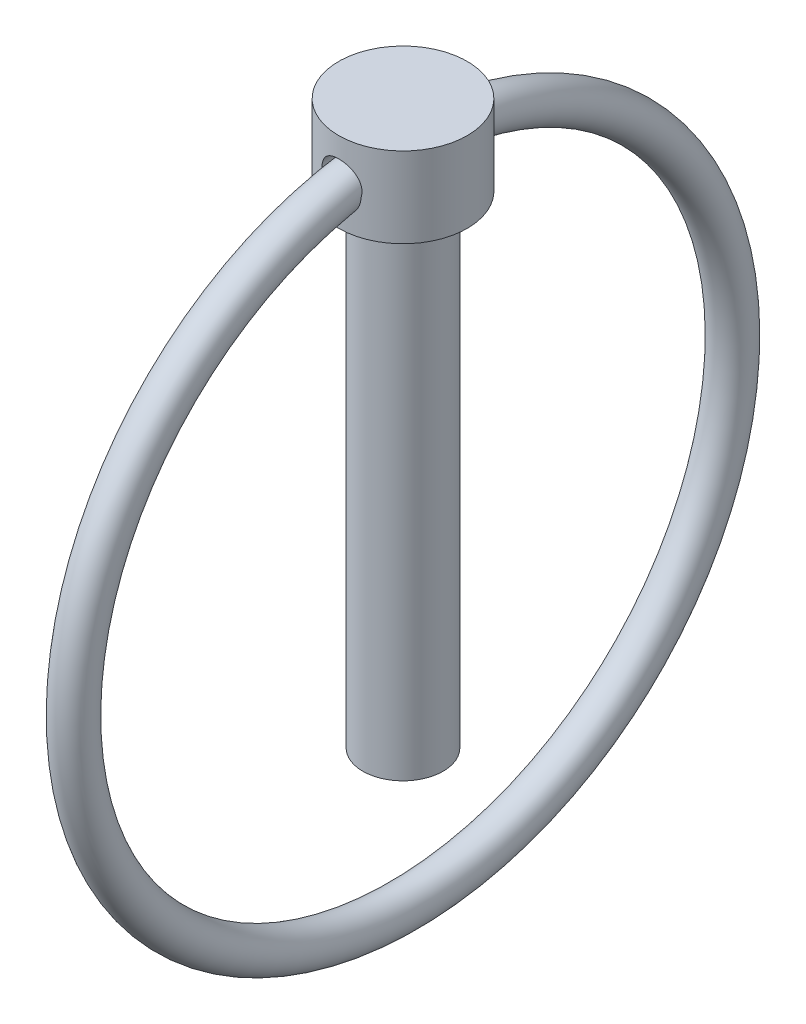
SolidWorks part; units mm, degrees
ref_plane "Front Plane" through (0, 0, 0) normal (0, 0, 1) x (1, 0, 0)
ref_plane "Top Plane" through (0, 0, 0) normal (0, 1, 0) x (1, 0, 0)
ref_plane "Right Plane" through (0, 0, 0) normal (1, 0, 0) x (0, 0, -1)
sketch "Sketch1" plane through (0, 0, 0) normal (0, 1, 0) x (1, 0, 0)
  circle A0 centre (0, 0) radius 2.5
  dimension "D1" = 5
extrude "Boss-Extrude1" add sketch "Sketch1" along normal blind 30
sketch "Sketch2" plane through (0, 30, 0) normal (0, 1, 0) x (1, 0, 0)
  circle A0 centre (0, 0) radius 4
  dimension "D1" = 8
extrude "Boss-Extrude2" add sketch "Sketch2" along normal blind 5
sketch "Sketch3" plane through (0, 0, 0) normal (0, 0, 1) x (1, 0, 0)
  line L0 (0, 35) -> (0, 30) construction
  line L1 (4, 35) -> (-4, 35) construction
  circle A0 centre (0, 32.5) radius 1.25
  point P2 (0, 32.6383)
  dimension "D1" = 2.5
  dimension "D2" = 2.5
extrude "Cut-Extrude1" cut sketch "Sketch3" against normal blind 5 and the other way blind 5
sketch "Sketch4" plane through (0, 0, 0) normal (0, 0, 1) x (1, 0, 0)
  line L0 (4, 35) -> (-4, 35) construction
  line L1 (-16.4966, 12) -> (32.3878, 12) construction
  circle A0 centre (0, 32.5) radius 1.2
  dimension "D1" = 2.4
  dimension "D2" = 2.5
  dimension "D3" = 12
revolve "Revolve2" add sketch "Sketch4" angle 360 about L1
